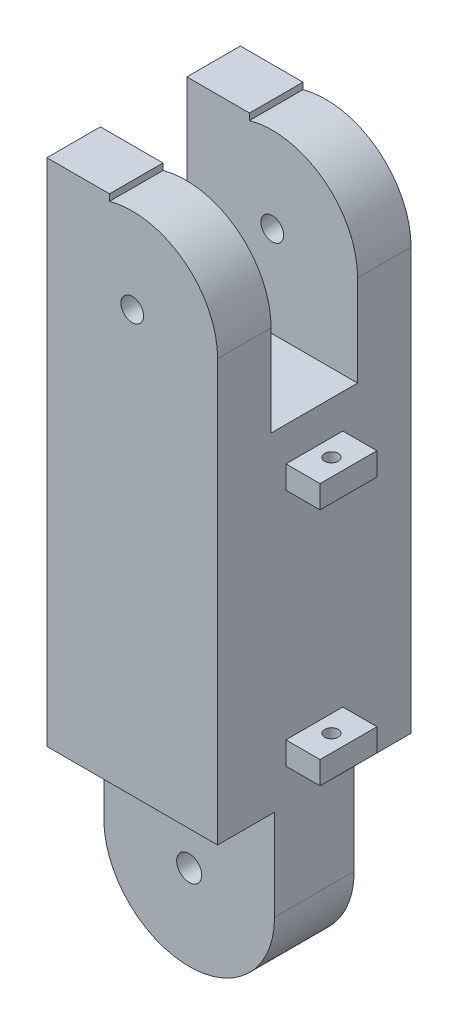
SolidWorks part; units mm, degrees
ref_plane "Front Plane" through (0, 0, 0) normal (0, 0, 1) x (1, 0, 0)
ref_plane "Top Plane" through (0, 0, 0) normal (0, 1, 0) x (1, 0, 0)
ref_plane "Right Plane" through (0, 0, 0) normal (1, 0, 0) x (0, 0, -1)
sketch "Finger_Skeleton" plane through (0, 0, 0) normal (0, 0, -1) x (-1, 0, 0)
  line L0 (0, 0) -> (0, 45)
  line L1 (0, 45) -> (0, 70)
  line L2 (0, 70) -> (0, 93)
  circle A1 centre (0, 0) radius 5 construction
  circle A2 centre (0, 45) radius 5 construction
  circle A3 centre (0, 70) radius 5 construction
  dimension "D4" = 10
  dimension "D5" = 10
  dimension "D6" = 10
  dimension "D1" = 45
  dimension "D2" = 25
  dimension "D3" = 23
sketch "Link1_Outline" plane through (0, 0, 0) normal (0, 0, 1) x (1, 0, 0)
  line L0 (0, 0) -> (0, 45) construction
  line L1 (-7.5, 0) -> (-7.5, 45)
  line L2 (7.5, 0) -> (7.5, 45)
  arc A0 (-7.5, 0) -> (7.5, 0) centre (0, 0) ccw
  arc A1 (7.5, 45) -> (-7.5, 45) centre (0, 45) ccw
  point P4 (0, 22.5)
  dimension "D1" = 15
extrude "Link1_Body" add sketch "Link1_Outline" along normal mid plane 17
sketch "Sketch1" plane through (7.5, 0, 0) normal (1, 0, 0) x (0, 0, -1)
  line L0 (0, 0) -> (0, 45) construction
  line L1 (3.5, -8) -> (9, -8)
  line L2 (3.5, -8) -> (3.5, 7.9981)
  line L3 (3.5, 7.9981) -> (9, 7.9981)
  line L4 (9, -8) -> (9, 7.9981)
  line L5 (-8.5, -7.5) -> (8.5, -7.5) construction
  line L6 (0, 55) -> (0, -55) construction
  line L7 (-9, -8) -> (-9, 7.9981)
  line L8 (-3.5, 7.9981) -> (-9, 7.9981)
  line L9 (-3.5, -8) -> (-3.5, 7.9981)
  line L10 (-3.5, -8) -> (-9, -8)
  dimension "D1" = 3.5
  dimension "D2" = 5.5
  dimension "D3" = 15.9981
  dimension "D4" = 0.5
extrude "Tongue_Cut" cut sketch "Sketch1" against normal through all both and the other way through all
sketch "Sketch7" plane through (0, 0, 0) normal (0, 0, 1) x (1, 0, 0)
  line L1 (-7.5, 45) -> (-2, 45)
  line L2 (-7.5, 45) -> (-7.5, 52.8)
  line L3 (-7.5, 52.8) -> (-2, 52.8)
  line L4 (-2, 45) -> (-2, 52.8)
  dimension "D1" = 5.5
  dimension "D2" = 7.8
extrude "Boss-Extrude1" add sketch "Sketch7" along normal mid plane 17
sketch "Sketch2" plane through (0, 0, 0) normal (1, 0, 0) x (0, 0, -1)
  line L0 (0, 0) -> (0, 45) construction
  line L1 (3.8, 37) -> (-3.8, 37)
  line L2 (3.8, 37) -> (3.8, 55)
  line L3 (3.8, 55) -> (-3.8, 55)
  line L4 (-3.8, 37) -> (-3.8, 55)
  dimension "D1" = 3.8
  dimension "D2" = 18
  dimension "D3" = 7.6
  dimension "D4" = 37
extrude "Slot_Cut" cut sketch "Sketch2" against normal through all both and the other way through all
sketch "Sketch3" plane through (0, 0, 0) normal (0, 0, 1) x (1, 0, 0)
  circle A0 centre (0, 0) radius 1.1
  circle A1 centre (0, 45) radius 1
  dimension "D1" = 2.2
  dimension "D2" = 2
extrude "Pin_Holes" cut sketch "Sketch3" against normal through all both and the other way through all
sketch "Sketch4" plane through (0, 0, 0) normal (0, 0, 1) x (1, 0, 0)
  line L0 (0, 0) -> (0, 45) construction
  line L1 (7, 13) -> (10.5, 13)
  line L2 (7, 13) -> (7, 11)
  line L3 (7, 11) -> (10.5, 11)
  line L4 (10.5, 13) -> (10.5, 11)
  dimension "D1" = 7
  dimension "D2" = 3.5
  dimension "D3" = 11
  dimension "D4" = 2
extrude "Guide_Block_1" add sketch "Sketch4" along normal mid plane 5
sketch "Sketch5" plane through (0, 0, 0) normal (0, 0, 1) x (1, 0, 0)
  line L0 (0, 0) -> (0, 45) construction
  line L1 (7.0006, 32) -> (10.5006, 32)
  line L2 (7.0006, 32) -> (7.0006, 34)
  line L3 (7.0006, 34) -> (10.5006, 34)
  line L4 (10.5006, 32) -> (10.5006, 34)
  dimension "D1" = 7.0006
  dimension "D2" = 32
  dimension "D3" = 3.5
  dimension "D4" = 2
extrude "Guide_Block_2" add sketch "Sketch5" along normal mid plane 5
sketch "Sketch6" plane through (0, 0, 0) normal (0, 1, 0) x (1, 0, 0)
  line L0 (10.5006, -2.5) -> (7.5, -2.5) construction
  circle A0 centre (9, 0) radius 0.6
  dimension "D1" = 1.2
  dimension "D2" = 9
  dimension "D3" = 2.5
extrude "Cord_Guides" cut sketch "Sketch6" along normal through all both and the other way through all
